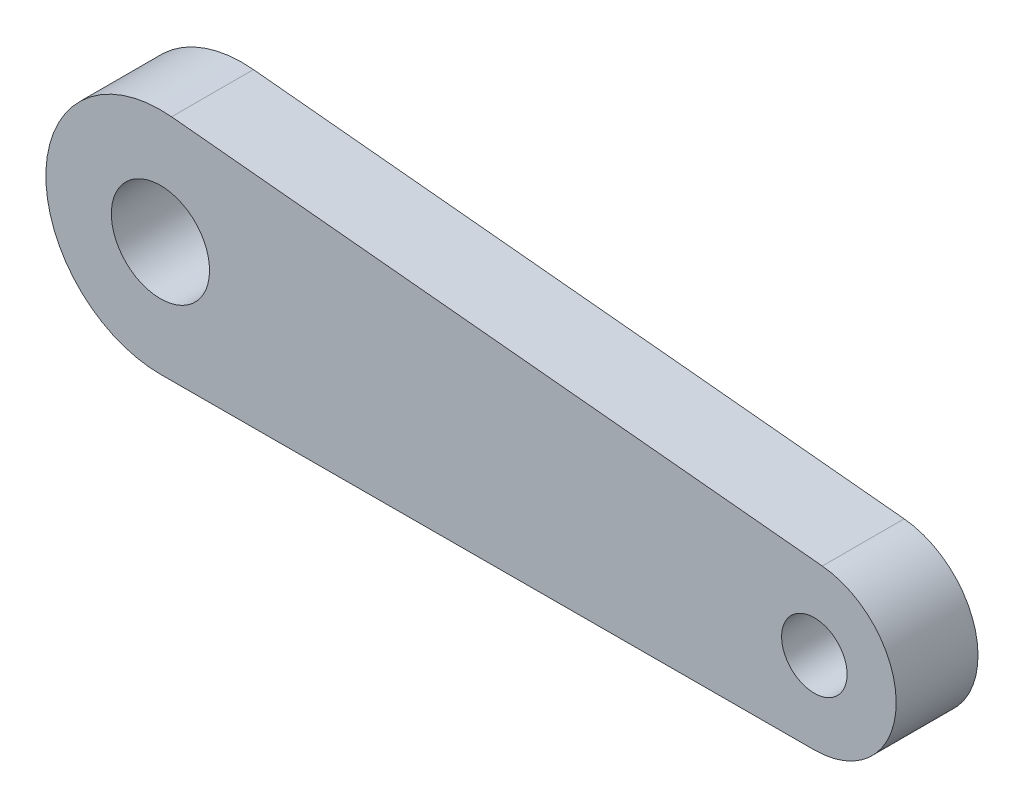
SolidWorks part; units mm, degrees
ref_plane "Front Plane" through (0, 0, 0) normal (0, 0, 1) x (1, 0, 0)
ref_plane "Top Plane" through (0, 0, 0) normal (0, 1, 0) x (1, 0, 0)
ref_plane "Right Plane" through (0, 0, 0) normal (1, 0, 0) x (0, 0, -1)
sketch "Sketch1" plane through (0, 0, 0) normal (0, 0, 1) x (1, 0, 0)
  line L0 (-59.3182, 16.9667) -> (-19.5582, 13.0755)
  line L1 (-20.0328, 3.0992) -> (-59.9826, 3)
  circle A0 centre (-60, 10) radius 3 construction
  circle A1 centre (-20.0452, 8.0992) radius 2 construction
  circle A2 centre (-60, 10) radius 3
  circle A3 centre (-20.0452, 8.0992) radius 2
  arc A4 (-19.5582, 13.0755) -> (-20.0328, 3.0992) centre (-20.0452, 8.0992) cw
  arc A5 (-59.9826, 3) -> (-59.3182, 16.9667) centre (-60, 10) cw
  dimension "D1" = 5
  dimension "D2" = 7
extrude "Boss-Extrude1" add sketch "Sketch1" along normal blind 5 from offset 10
